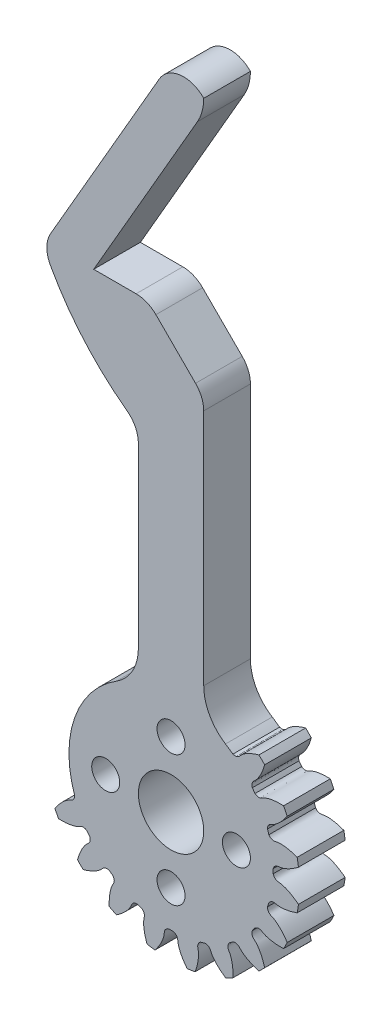
SolidWorks part; units mm, degrees
material "聚脂树脂"
ref_plane "前视基准面" through (0, 0, 0) normal (0, 0, 1) x (1, 0, 0)
ref_plane "上视基准面" through (0, 0, 0) normal (0, 1, 0) x (1, 0, 0)
ref_plane "右视基准面" through (0, 0, 0) normal (1, 0, 0) x (0, 0, -1)
other "Configuration Table"
sketch "草图1" plane through (0, 0, 0) normal (0, 0, 1) x (1, 0, 0)
  circle A0 centre (0, 0) radius 13.75
extrude "凸台-拉伸1" add sketch "草图1" along normal blind 5
ref_axis "基准轴1" through (0, 0, -1.5) along (0, 0, 1)
sketch "草图2" plane through (0, 0, 0) normal (0, 0, 1) x (1, 0, 0)
  line L0 (0, 0) -> (0, 13.75) construction
  circle A0 centre (0, 0) radius 13.75 construction
  arc A1 (0.2416, 10.9348) -> (-0.2416, 10.9348) centre (0, 0) ccw
  arc A2 (3.9764, 15.6228) -> (-3.9764, 15.6228) centre (0, 0) ccw
  spline S0 degree 3 poles (0.2416, 10.9348) (0.764, 11.1168) (0.6964, 11.4839) (0.7661, 11.8375) (0.7736, 11.8719) (0.7829, 11.9108) (0.7941, 11.954) (0.8075, 12.0015) (0.8231, 12.0532) (0.8413, 12.1091) (0.8621, 12.169) (0.8857, 12.2329) (0.9123, 12.3007) (0.9421, 12.3723) (0.9752, 12.4476) (1.0117, 12.5264) (1.0519, 12.6088) (1.0959, 12.6945) (1.1438, 12.7834) (1.1957, 12.8755) (1.2519, 12.9705) (1.3125, 13.0684) (1.3775, 13.1691) (1.4472, 13.2723) (1.5216, 13.3779) (1.601, 13.4858) (1.6853, 13.5958) (1.7747, 13.7078) (1.8694, 13.8216) (1.9693, 13.937) (2.0748, 14.0539) (2.1857, 14.1721) (2.3023, 14.2914) (2.4246, 14.4116) (2.5527, 14.5326) (2.6866, 14.6542) (2.8265, 14.7761) (2.9725, 14.8983) (3.1245, 15.0204) (3.2826, 15.1424) (3.4469, 15.2639) (3.6768, 15.427) (3.8549, 15.5454) (3.9764, 15.6228) knots 0 0 0 0 0.165916 0.170906 0.176664 0.183189 0.190482 0.198542 0.207371 0.216967 0.22733 0.238462 0.250361 0.263027 0.276462 0.290664 0.305634 0.321371 0.337876 0.355149 0.37319 0.391998 0.411574 0.431917 0.453028 0.474907 0.497554 0.520968 0.54515 0.570099 0.595817 0.622302 0.649554 0.677575 0.706363 0.735918 0.766242 0.797333 0.829191 0.861818 0.895212 0.929373 1 1 1 1
  spline S1 degree 3 poles (-0.2416, 10.9348) (-0.764, 11.1168) (-0.6964, 11.4839) (-0.7661, 11.8375) (-0.7736, 11.8719) (-0.7829, 11.9108) (-0.7941, 11.954) (-0.8075, 12.0015) (-0.8231, 12.0532) (-0.8413, 12.1091) (-0.8621, 12.169) (-0.8857, 12.2329) (-0.9123, 12.3007) (-0.9421, 12.3723) (-0.9752, 12.4476) (-1.0117, 12.5264) (-1.0519, 12.6088) (-1.0959, 12.6945) (-1.1438, 12.7834) (-1.1957, 12.8755) (-1.2519, 12.9705) (-1.3125, 13.0684) (-1.3775, 13.1691) (-1.4472, 13.2723) (-1.5216, 13.3779) (-1.601, 13.4858) (-1.6853, 13.5958) (-1.7747, 13.7078) (-1.8694, 13.8216) (-1.9693, 13.937) (-2.0748, 14.0539) (-2.1857, 14.1721) (-2.3023, 14.2914) (-2.4246, 14.4116) (-2.5527, 14.5326) (-2.6866, 14.6542) (-2.8265, 14.7761) (-2.9725, 14.8983) (-3.1245, 15.0204) (-3.2826, 15.1424) (-3.4469, 15.2639) (-3.6768, 15.427) (-3.8549, 15.5454) (-3.9764, 15.6228) knots 0 0 0 0 0.165916 0.170906 0.176664 0.183189 0.190482 0.198542 0.207371 0.216967 0.22733 0.238462 0.250361 0.263027 0.276462 0.290664 0.305634 0.321371 0.337876 0.355149 0.37319 0.391998 0.411574 0.431917 0.453028 0.474907 0.497554 0.520968 0.54515 0.570099 0.595817 0.622302 0.649554 0.677575 0.706363 0.735918 0.766242 0.797333 0.829191 0.861818 0.895212 0.929373 1 1 1 1
extrude "切除-拉伸1" cut sketch "草图2" along normal through all
pattern_circular "阵列(圆周)1" count 20 every 18 about axis through (0, 0, -1.5) along (0, 0, 1) of "切除-拉伸1"
sketch "草图6" plane through (0, 0, 0) normal (0, 0, -1) x (-1, 0, 0)
  line L0 (0, 0) -> (0, 65.9124) construction
  line L1 (0, 0) -> (39.45, 0) construction
  line L2 (0, 0) -> (-30.8379, 0) construction
  line L3 (-12.5, 0) -> (-12.5, 56.4778) construction
  line L4 (3.5, 0) -> (3.5, 35.9714)
  line L5 (-3.5, 0) -> (-3.5, 35.9714)
  line L6 (-3.5, 35.9714) -> (-3.5, 73.8085)
  line L7 (-3.5, 73.8085) -> (-12.5, 58.22) construction
  line L8 (-3.5, 73.8085) -> (6.3052, 90.7916) construction
  line L9 (-3.5, 73.8085) -> (1.2022, 81.9529)
  line L10 (-3.5, 0) -> (3.5, 0)
  line L11 (-5.8534, 12.4419) -> (-3.5, 13.8006)
  line L12 (5.8534, 12.4419) -> (3.5, 13.8006)
  line L13 (-12.5, 82.22) -> (-33.2846, 46.22)
  line L14 (-33.2846, 46.22) -> (8.2846, 46.22)
  line L15 (8.2846, 46.22) -> (-12.5, 82.22)
  line L16 (-3.5, 75.6315) -> (13.7137, 45.8166)
  line L17 (-3.5, 73.8085) -> (-3.5, 75.6315)
  circle A0 centre (0, 0) radius 12.5 construction
  circle A1 centre (-12.5, 58.22) radius 24 construction
  circle A2 centre (-12.5, 58.22) radius 27.4044 construction
  arc A3 (1.2022, 81.9529) -> (3.5, 35.9714) centre (-12.5, 58.22) cw
  arc A4 (-0.5, 79.0046) -> (-3.5, 35.9714) centre (-12.5, 58.22) cw
  arc A5 (3.5, 34.0332) -> (13.7137, 45.8166) centre (-12.5, 58.22) ccw
  arc A6 (7.7846, 47.086) -> (7.2846, 46.22) centre (8.2846, 46.22) cw
  spline S0 degree 3 poles (2502.66, 1658.782) (-28.7069, -14.6032) (-1.7191, 6.2407) (-4.3931, 11.033) (-4.4189, 11.076) (-4.4589, 11.1387) (-4.5098, 11.2131) (-4.5827, 11.3111) (-4.6712, 11.4208) (-4.7765, 11.541) (-4.8994, 11.6706) (-5.0408, 11.8083) (-5.2016, 11.9528) (-5.3825, 12.1027) (-5.5474, 12.2287) (-5.6899, 12.331) (-28.3078, 27.8963) (-140.1993, -89.1599) (2777.6606, 1130.6237) knots -2.506621 -2.506621 -2.506621 -2.506621 0.165916 0.170906 0.183189 0.190482 0.207371 0.22733 0.250361 0.276462 0.305634 0.337876 0.37319 0.411574 0.453028 0.474907 0.497554 13.91055 13.91055 13.91055 13.91055 only from (-3.6089, 10.325) to (-5.8534, 12.4419) construction
  spline S1 degree 3 poles (-3.5, 10.3269) (-4.1564, 10.2919) (-4.2008, 10.6883) (-4.3931, 11.033) (-4.4189, 11.076) (-4.4589, 11.1387) (-4.5098, 11.2131) (-4.5827, 11.3111) (-4.6712, 11.4208) (-4.7765, 11.541) (-4.8994, 11.6706) (-5.0408, 11.8083) (-5.2016, 11.9528) (-5.3825, 12.1027) (-5.5842, 12.2567) (-5.7442, 12.3691) (-5.8366, 12.4308) (-5.8534, 12.4419) knots -0.010289 -0.010289 -0.010289 -0.010289 0.165916 0.170906 0.183189 0.190482 0.207371 0.22733 0.250361 0.276462 0.305634 0.337876 0.37319 0.411574 0.453028 0.497554 0.507432 0.507432 0.507432 0.507432
  spline S2 degree 3 poles (-2502.66, 1658.782) (28.7069, -14.6032) (1.7191, 6.2407) (4.3931, 11.033) (4.4189, 11.076) (4.4589, 11.1387) (4.5098, 11.2131) (4.5827, 11.3111) (4.6712, 11.4208) (4.7765, 11.541) (4.8994, 11.6706) (5.0408, 11.8083) (5.2016, 11.9528) (5.3825, 12.1027) (5.5474, 12.2287) (5.6899, 12.331) (28.3078, 27.8963) (140.1993, -89.1599) (-2777.6606, 1130.6237) knots -2.014052 -2.014052 -2.014052 -2.014052 0.658484 0.663474 0.675757 0.68305 0.699939 0.719899 0.742929 0.76903 0.798202 0.830445 0.865758 0.904142 0.945597 0.967475 0.990122 14.403118 14.403118 14.403118 14.403118 only from (3.6089, 10.325) to (5.8534, 12.4419) construction
  spline S3 degree 3 poles (3.5, 10.3269) (4.1564, 10.2919) (4.2008, 10.6883) (4.3931, 11.033) (4.4189, 11.076) (4.4589, 11.1387) (4.5098, 11.2131) (4.5827, 11.3111) (4.6712, 11.4208) (4.7765, 11.541) (4.8994, 11.6706) (5.0408, 11.8083) (5.2016, 11.9528) (5.3825, 12.1027) (5.5842, 12.2567) (5.7442, 12.3691) (5.8366, 12.4308) (5.8534, 12.4419) knots 0.482279 0.482279 0.482279 0.482279 0.658484 0.663474 0.675757 0.68305 0.699939 0.719899 0.742929 0.76903 0.798202 0.830445 0.865758 0.904142 0.945597 0.990122 1 1 1 1
  dimension "D1" = 25
  dimension "D4" = 48
  dimension "D5" = 30
  dimension "D8" = 60
  dimension "D10" = 29
  dimension "D11" = 1
  dimension "D2" = 7
  dimension "D3" = 58.22
  dimension "D6" = 60
  dimension "D7" = 60
  dimension "D9" = 4.5
extrude "凸台-拉伸2" add sketch "草图6" against normal blind 5 contours A3 L9 L6 L5 L10 L4 | S1 L5 L11 | L4 S3 L12 | A4 L16 L6 L15 | A4 L14 L6 | L4 A5 L16 A3 | A6 A4 | A6 A4 L14 | A6 L15 A4 | L17 L9 L16 region at (-1.2608, 22.5789, 0) region at (-4.2531, 12.1172, 0) region at (4.2531, 12.1172, 0) region at (-8.897, 40.379, 0) region at (-0.8059, 42.391, 0) region at (-7.731, 45.9061, 0) region at (-8.6489, 46.0097, 0) region at (-2.9999, 60.0044, 0) region at (-8.2796, 46.8564, 0) region at (3.3246, 74.72, 0)
ref_plane "基准面1" through (12.5, 0, 0) normal (1, 0, 0) x (0, 0, -1)
sketch "草图4" plane through (0, 0, 5) normal (0, 0, 1) x (1, 0, 0)
  line L0 (0, 0) -> (0, 14.4175) construction
  line L1 (0, 0) -> (19.7904, 0) construction
  circle A0 centre (0, 0) radius 9
  circle A1 centre (0, 0) radius 3.5
  circle A2 centre (0, 7) radius 1.5
  circle A3 centre (7, 0) radius 1.5
  circle A4 centre (0, -7) radius 1.5
  circle A5 centre (-7, 0) radius 1.5
  dimension "D1" = 18
  dimension "D2" = 7
  dimension "D3" = 3
  dimension "D4" = 3
  dimension "D5" = 7
  dimension "D6" = 7
extrude "切除-拉伸2" cut sketch "草图4" against normal blind 20 contours A1 | A5 | A2 | A3 | A4
ref_plane "基准面2" through (0, 0, 9) normal (0, 0, 1) x (1, 0, 0)
sketch "草图17" plane through (0, 0, 5) normal (0, 0, 1) x (1, 0, 0)
  line L0 (0, 0) -> (-6.6228, 8.7044)
  line L1 (-6.6228, 8.7044) -> (-11.857, 15.5837)
  line L2 (0, 0) -> (-10.325, -3.6089)
  line L3 (-10.325, -3.6089) -> (-17.9409, -6.2709)
  circle A0 centre (0, 0) radius 10.9375
  arc A1 (-6.2318, 8.9885) -> (-6.6228, 8.7044) centre (0, 0) ccw construction
  circle A2 centre (0, 0) radius 17.5
  dimension "D1" = 35
extrude "切除-拉伸5" cut sketch "草图17" against normal blind 10 contours L1 A2 L3 A0 region at (-12.9643, 3.8979, 5)
sketch "草图20" plane through (0, 0, 0) normal (0, 0, -1) x (-1, 0, 0)
  line L0 (-3.5, 13.8006) -> (-3.5, 10.3624)
  line L1 (3.5, 13.8006) -> (3.5, 10.3624)
  line L2 (5.8534, 12.4419) -> (3.5, 13.8006) construction
  line L3 (-5.8534, 12.4419) -> (-3.5, 13.8006) construction
  line L4 (5.8534, 12.4419) -> (3.5, 13.8006)
  line L5 (-5.8534, 12.4419) -> (-3.5, 13.8006)
  circle A0 centre (0, 0) radius 10.9375
  arc A1 (10.325, -3.6089) -> (6.2318, 8.9885) centre (0, 0) ccw construction
  arc A2 (6.6252, 12.0486) -> (5.8534, 12.4419) centre (0, 0) ccw construction
  arc A3 (-5.8534, 12.4419) -> (-6.6252, 12.0486) centre (0, 0) ccw construction
  arc A4 (6.6252, 12.0486) -> (5.8534, 12.4419) centre (0, 0) ccw
  arc A5 (-5.8534, 12.4419) -> (-6.6252, 12.0486) centre (0, 0) ccw
  spline S0 degree 3 poles (1876.625, -698.848) (-20.9969, 12.4766) (4.3246, 5.6774) (6.3437, 10.0391) (6.3633, 10.0853) (6.3905, 10.1545) (6.4208, 10.2394) (6.4573, 10.356) (6.4939, 10.4921) (6.5293, 10.6479) (6.5619, 10.8235) (6.5902, 11.0188) (6.6126, 11.2338) (6.6276, 11.4683) (6.6325, 11.6758) (6.6315, 11.8512) (6.0134, 36.0214) (-118.4428, 55.7409) (1694.3797, -1060.7669) knots -2.172632 -2.172632 -2.172632 -2.172632 0.165916 0.170906 0.183189 0.190482 0.207371 0.22733 0.250361 0.276462 0.305634 0.337876 0.37319 0.411574 0.453028 0.474907 0.497554 12.30377 12.30377 12.30377 12.30377 only from (6.2318, 8.9885) to (6.6252, 12.0486) construction
  spline S1 degree 3 poles (-1876.625, -698.848) (20.9969, 12.4766) (-4.3246, 5.6774) (-6.3437, 10.0391) (-6.3633, 10.0853) (-6.3905, 10.1545) (-6.4208, 10.2394) (-6.4573, 10.356) (-6.4939, 10.4921) (-6.5293, 10.6479) (-6.5619, 10.8235) (-6.5902, 11.0188) (-6.6126, 11.2338) (-6.6276, 11.4683) (-6.6325, 11.6758) (-6.6315, 11.8512) (-6.0134, 36.0214) (118.4428, 55.7409) (-1694.3797, -1060.7669) knots -1.680063 -1.680063 -1.680063 -1.680063 0.658484 0.663474 0.675757 0.68305 0.699939 0.719899 0.742929 0.76903 0.798202 0.830445 0.865758 0.904142 0.945597 0.967475 0.990122 12.796339 12.796339 12.796339 12.796339 only from (-6.2318, 8.9885) to (-6.6252, 12.0486) construction
  spline S2 degree 3 poles (6.2318, 8.9885) (5.9162, 9.4428) (6.1867, 9.7) (6.3437, 10.0391) (6.3633, 10.0853) (6.3905, 10.1545) (6.4208, 10.2394) (6.4573, 10.356) (6.4939, 10.4921) (6.5293, 10.6479) (6.5619, 10.8235) (6.5902, 11.0188) (6.6126, 11.2338) (6.6276, 11.4683) (6.6336, 11.722) (6.6305, 11.9176) (6.6261, 12.0285) (6.6252, 12.0486) knots 0 0 0 0 0.165916 0.170906 0.183189 0.190482 0.207371 0.22733 0.250361 0.276462 0.305634 0.337876 0.37319 0.411574 0.453028 0.497554 0.507432 0.507432 0.507432 0.507432
  spline S3 degree 3 poles (-6.2318, 8.9885) (-5.9162, 9.4428) (-6.1867, 9.7) (-6.3437, 10.0391) (-6.3633, 10.0853) (-6.3905, 10.1545) (-6.4208, 10.2394) (-6.4573, 10.356) (-6.4939, 10.4921) (-6.5293, 10.6479) (-6.5619, 10.8235) (-6.5902, 11.0188) (-6.6126, 11.2338) (-6.6276, 11.4683) (-6.6336, 11.722) (-6.6305, 11.9176) (-6.6261, 12.0285) (-6.6252, 12.0486) knots 0.492568 0.492568 0.492568 0.492568 0.658484 0.663474 0.675757 0.68305 0.699939 0.719899 0.742929 0.76903 0.798202 0.830445 0.865758 0.904142 0.945597 0.990122 1 1 1 1
extrude "切除-拉伸7" cut sketch "草图20" against normal blind 10 contours S3 A0 L0 L5 A5 | A0 S2 A4 L4 L1 region at (4.956, 11.3958, 0) region at (-4.956, 11.3958, 0)
fillet "圆角7" radius 5 2 edges at (-3.5, 10.3624, 2.5) (3.5, 10.3624, 2.5)
fillet "圆角8" radius 3 2 edges at (-13.7137, 45.8166, 2.5) (-3.5, 34.0332, 2.5)
chamfer "倒角1" distance 6 angle 45 1 edges at (3.5, 46.22, 2.5)
fillet "圆角10" radius 3 2 edges at (-2.5, 46.22, 2.5) (3.5, 40.22, 2.5)
fillet "圆角11" radius 5 1 edges at (3.5, 66.6315, 2.5)
fillet "圆角12" radius 3 1 edges at (3.5, 75.6315, 2.5)
